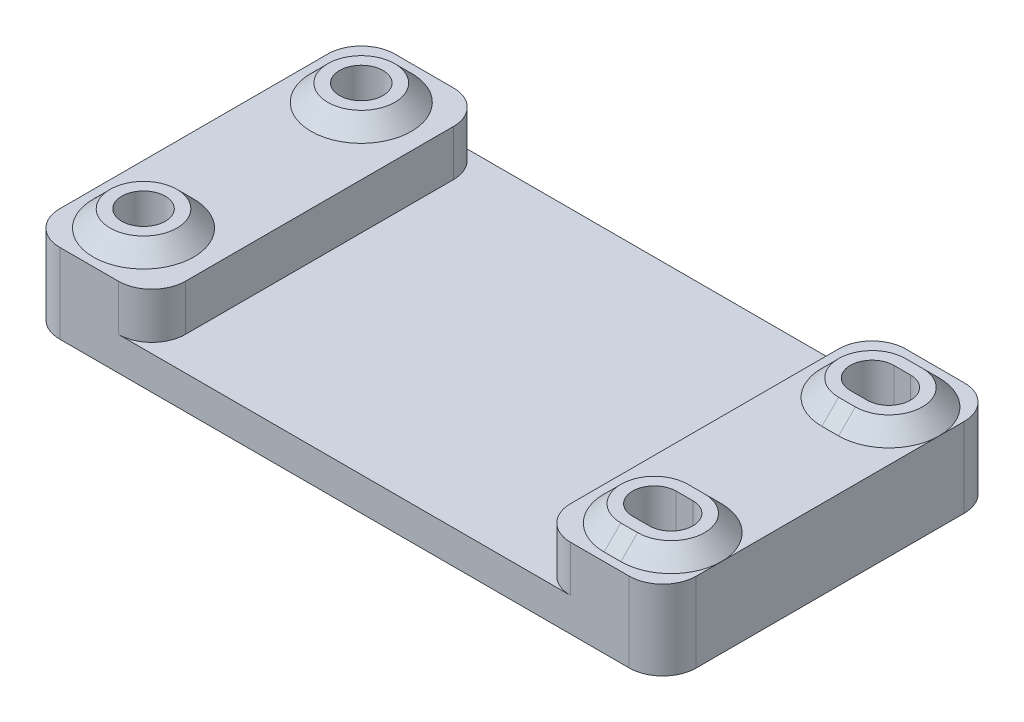
SolidWorks part; units mm, degrees
ref_plane "Front Plane" through (0, 0, 0) normal (0, 0, 1) x (1, 0, 0)
ref_plane "Top Plane" through (0, 0, 0) normal (0, 1, 0) x (1, 0, 0)
ref_plane "Right Plane" through (0, 0, 0) normal (1, 0, 0) x (0, 0, -1)
sketch "Sketch1" plane through (0, 0, 0) normal (0, 1, 0) x (1, 0, 0)
  line L0 (-31, 0) -> (31, 0) construction
  line L1 (31, -13) -> (31, 10.4) construction
  line L2 (31, 0) -> (38, 0)
  line L3 (38, -20) -> (38, 20)
  line L4 (38, 20) -> (-38, 20)
  line L5 (0, 0) -> (0, 26.2174) construction
  line L6 (38, -20) -> (-38, -20)
  line L7 (-38, -20) -> (-38, 20)
  line L8 (-31, 0) -> (-38, 0)
  line L9 (-31, -13) -> (-31, 13) construction
  line L10 (31, 13) -> (32, 13)
  line L11 (31, 13) -> (30, 13)
  line L12 (30, 15.6) -> (32, 15.6)
  line L13 (32, 10.4) -> (30, 10.4)
  line L14 (31, 10.6) -> (31, 13) construction
  line L15 (32, -10.4) -> (30, -10.4)
  line L16 (30, -15.6) -> (32, -15.6)
  circle A2 centre (-31, -13) radius 2.6
  circle A3 centre (-31, 13) radius 2.6
  arc A4 (32, 10.4) -> (32, 15.6) centre (32, 13) ccw
  arc A5 (30, 15.6) -> (30, 10.4) centre (30, 13) ccw
  arc A7 (32, -10.4) -> (32, -15.6) centre (32, -13) cw
  arc A8 (30, -15.6) -> (30, -10.4) centre (30, -13) cw
  point P18 (0, -20)
  point P19 (0, 20)
  dimension "D1" = 62
  dimension "D2" = 26
  dimension "D3" = 7
  dimension "D4" = 40
extrude "Boss-Extrude1" add sketch "Sketch1" along normal blind 4
sketch "Sketch2" plane through (0, 4, 0) normal (0, 1, 0) x (1, 0, 0)
  line L0 (23, 20) -> (38, 20)
  line L1 (38, 20) -> (-38, 20) construction
  line L3 (38, 20) -> (38, -20)
  line L4 (38, -20) -> (23, -20)
  line L5 (38, -20) -> (-38, -20) construction
  line L6 (23, -20) -> (23, 20)
  line L8 (0, 0) -> (0, 6.4774) construction
  line L9 (-23, -20) -> (-23, 20)
  line L10 (-38, -20) -> (-23, -20)
  line L11 (-38, 20) -> (-38, -20)
  line L12 (-23, 20) -> (-38, 20)
  line L13 (30, 15.6) -> (32, 15.6)
  line L14 (32, 10.4) -> (30, 10.4)
  line L15 (30, -10.4) -> (32, -10.4)
  line L16 (32, -15.6) -> (30, -15.6)
  circle A0 centre (-31, 13) radius 2.6
  circle A1 centre (-31, -13) radius 2.6
  circle A4 centre (-31, 13) radius 2.6
  circle A5 centre (-31, -13) radius 2.6
  arc A6 (30, 15.6) -> (30, 10.4) centre (30, 13) ccw
  arc A7 (32, 10.4) -> (32, 15.6) centre (32, 13) ccw
  arc A8 (32, -15.6) -> (32, -10.4) centre (32, -13) ccw
  arc A9 (30, -10.4) -> (30, -15.6) centre (30, -13) ccw
extrude "Boss-Extrude2" add sketch "Sketch2" along normal blind 5.5
sketch "Sketch3" plane through (0, 9.5, 0) normal (0, 1, 0) x (1, 0, 0)
  line L0 (32, 17) -> (30, 17)
  line L1 (32, 9) -> (30, 9)
  line L2 (30, 15.6) -> (32, 15.6)
  line L3 (32, 10.4) -> (30, 10.4)
  line L6 (32, -10.4) -> (30, -10.4)
  line L7 (30, -15.6) -> (32, -15.6)
  line L8 (32, -9) -> (30, -9)
  line L9 (32, -17) -> (30, -17)
  circle A0 centre (-31, 13) radius 2.6
  circle A1 centre (-31, 13) radius 4
  circle A2 centre (-31, -13) radius 2.6
  circle A3 centre (-31, -13) radius 4
  arc A8 (30, 17) -> (30, 9) centre (30, 13) ccw
  arc A9 (32, 9) -> (32, 17) centre (32, 13) ccw
  arc A10 (30, 15.6) -> (30, 10.4) centre (30, 13) ccw
  arc A11 (32, 10.4) -> (32, 15.6) centre (32, 13) ccw
  arc A12 (32, -10.4) -> (32, -15.6) centre (32, -13) cw
  arc A13 (30, -15.6) -> (30, -10.4) centre (30, -13) cw
  arc A14 (32, -9) -> (32, -17) centre (32, -13) cw
  arc A15 (30, -17) -> (30, -9) centre (30, -13) cw
extrude "Boss-Extrude3" add sketch "Sketch3" along normal blind 2
chamfer "Chamfer1" distance 2 angle 45 10 edges at (-31, 9.5, 17) (-31, 9.5, -9) (31, 9.5, -17) (26, 9.5, -13) (31, 9.5, -9) (36, 9.5, -13) (31, 9.5, 9) (26, 9.5, 13) (36, 9.5, 13) (31, 9.5, 17)
fillet "Fillet1" radius 4 8 edges at (38, 4.75, -20) (38, 4.75, 20) (23, 6.75, 20) (23, 6.75, -20) (-23, 6.75, 20) (-23, 6.75, -20) (-38, 4.75, -20) (-38, 4.75, 20)
